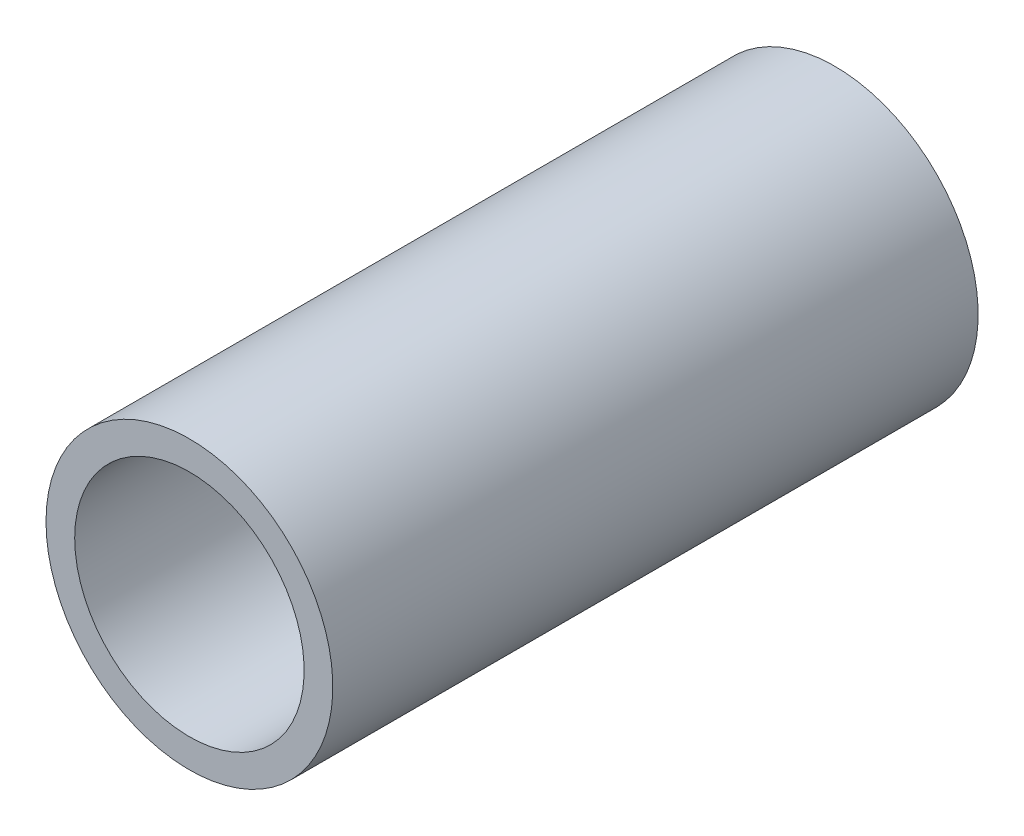
SolidWorks part; units mm, degrees
ref_plane "Ön Düzlem" through (0, 0, 0) normal (0, 0, 1) x (1, 0, 0)
ref_plane "Üst Düzlem" through (0, 0, 0) normal (0, 1, 0) x (1, 0, 0)
ref_plane "Sağ Düzlem" through (0, 0, 0) normal (1, 0, 0) x (0, 0, -1)
sketch "Sketch1" plane through (0, 0, 0) normal (0, 0, 1) x (1, 0, 0)
  circle A0 centre (0, 0) radius 8
  circle A1 centre (0, 0) radius 10
  dimension "D1" = 20
  dimension "D2" = 2
extrude "Boss-Extrude1" add sketch "Sketch1" along normal blind 45
ref_axis "Axis1" through (0, 0, 45) along (0, 0, -1)
